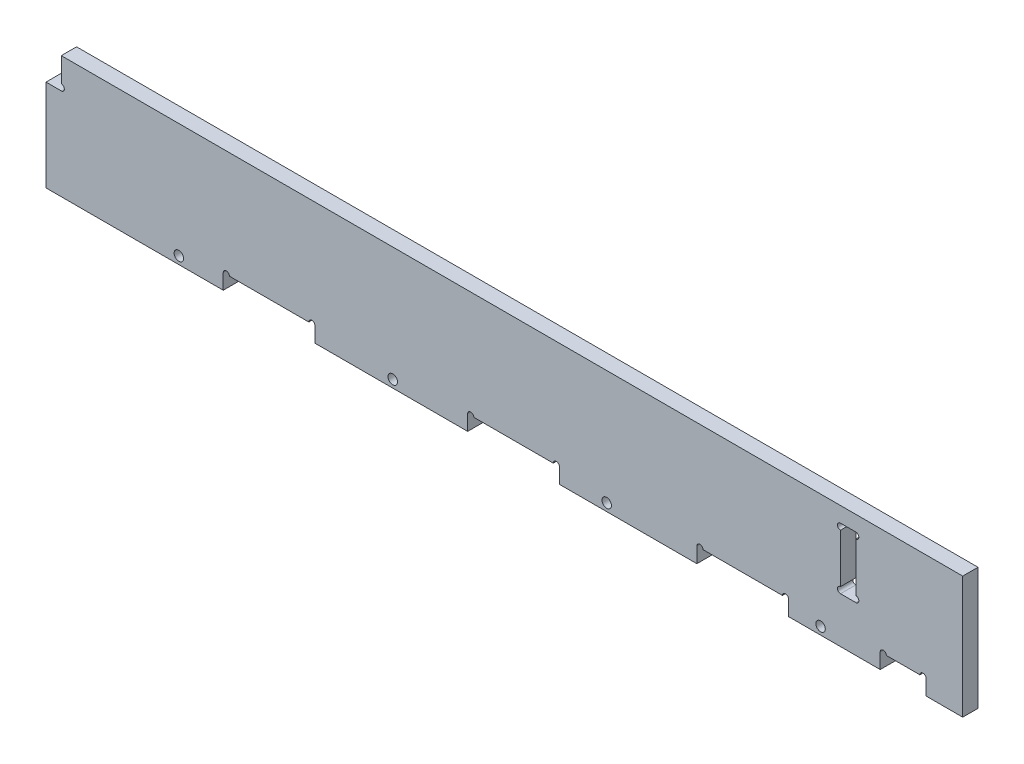
SolidWorks part; units mm, degrees
ref_plane "정면" through (0, 0, 0) normal (0, 0, 1) x (1, 0, 0)
ref_plane "윗면" through (0, 0, 0) normal (0, 1, 0) x (1, 0, 0)
ref_plane "우측면" through (0, 0, 0) normal (1, 0, 0) x (0, 0, -1)
sketch "스케치1" plane through (0, 0, 0) normal (0, 0, 1) x (1, 0, 0)
  line L1 (0, 0) -> (300, 0)
  line L2 (0, 0) -> (0, 40)
  line L3 (0, 40) -> (300, 40)
  line L4 (300, 0) -> (300, 40)
  dimension "D1" = 40
  dimension "D2" = 300
extrude "보스-돌출1" add sketch "스케치1" along normal blind 5
sketch "스케치2" plane through (0, 0, 5) normal (0, 0, 1) x (1, 0, 0)
  line L0 (0, 40) -> (0, 0) construction
  line L1 (5, 40) -> (0, 40)
  line L2 (5, 40) -> (5, 30)
  line L3 (5, 30) -> (0, 30)
  line L4 (0, 40) -> (0, 30)
  line L5 (5, 30) -> (0, 30) construction
  line L6 (0, 0) -> (300, 0) construction
  line L7 (58, 5) -> (88, 5)
  line L8 (58, 5) -> (58, 0)
  line L9 (58, 0) -> (88, 0)
  line L10 (88, 5) -> (88, 0)
  line L11 (88, 5) -> (88, 0) construction
  line L12 (168, 5) -> (168, 0) construction
  line L13 (168, 0) -> (138, 0)
  line L14 (168, 0) -> (168, 5)
  line L15 (168, 5) -> (138, 5)
  line L16 (138, 0) -> (138, 5)
  line L17 (243, 5) -> (243, 0) construction
  line L18 (243, 0) -> (213, 0)
  line L19 (243, 0) -> (243, 5)
  line L20 (243, 5) -> (213, 5)
  line L21 (213, 0) -> (213, 5)
  line L22 (288, 5) -> (288, 0) construction
  line L23 (288, 0) -> (273, 0)
  line L24 (288, 0) -> (288, 5)
  line L25 (288, 5) -> (273, 5)
  line L26 (273, 0) -> (273, 5)
  line L28 (260, 35) -> (265, 35)
  line L29 (260, 35) -> (260, 15)
  line L30 (260, 15) -> (265, 15)
  line L31 (265, 35) -> (265, 15)
extrude "컷-돌출1" cut sketch "스케치2" against normal blind 5
sketch "스케치3" plane through (0, 0, 5) normal (0, 0, 1) x (1, 0, 0)
  line L0 (265, 35) -> (260, 35) construction
  line L1 (260, 15) -> (265, 15) construction
  line L4 (243, 5) -> (213, 5) construction
  line L5 (88, 5) -> (58, 5) construction
  line L6 (168, 5) -> (138, 5) construction
  line L7 (5, 30) -> (5, 40) construction
  line L8 (288, 5) -> (273, 5) construction
  line L9 (273, 5) -> (273, 0) construction
  line L10 (288, 0) -> (288, 5) construction
  circle A0 centre (274, 5) radius 1
  circle A1 centre (287, 5) radius 1
  circle A2 centre (260, 16) radius 1
  circle A3 centre (265, 16) radius 1
  circle A4 centre (265, 34) radius 1
  circle A5 centre (260, 34) radius 1
  circle A6 centre (214, 5) radius 1
  circle A7 centre (242, 5) radius 1
  circle A8 centre (87, 5) radius 1
  circle A9 centre (139, 5) radius 1
  circle A10 centre (167, 5) radius 1
  circle A11 centre (5, 31) radius 1
  circle A13 centre (59, 5) radius 1
  dimension "D1" = 2
  dimension "D2" = 2
extrude "컷-돌출2" cut sketch "스케치3" against normal blind 5
sketch "스케치4" plane through (0, 0, 0) normal (0, 0, -1) x (-1, 0, 0)
  line L0 (-45.0287, 2.5) -> (-41.9287, 2.5) construction
  line L3 (-45.0287, 5) -> (-45.0287, 0) construction
  line L6 (-41.9287, 5) -> (-41.9287, 0) construction
  line L9 (-115.0287, 2.5) -> (-111.9287, 2.5) construction
  line L10 (-115.0287, 5) -> (-115.0287, 0) construction
  line L11 (-111.9287, 5) -> (-111.9287, 0) construction
  line L12 (-185.0287, 2.5) -> (-181.9287, 2.5) construction
  line L13 (-185.0287, 5) -> (-185.0287, 0) construction
  line L14 (-181.9287, 5) -> (-181.9287, 0) construction
  line L15 (-255.0287, 2.5) -> (-251.9287, 2.5) construction
  line L16 (-255.0287, 5) -> (-255.0287, 0) construction
  line L17 (-251.9287, 5) -> (-251.9287, 0) construction
  circle A0 centre (-253.4787, 2.5) radius 1.55
  circle A1 centre (-183.4787, 2.5) radius 1.55
  circle A2 centre (-113.4787, 2.5) radius 1.55
  circle A3 centre (-43.4787, 2.5) radius 1.55
extrude "컷-돌출3" cut sketch "스케치4" against normal blind 10
